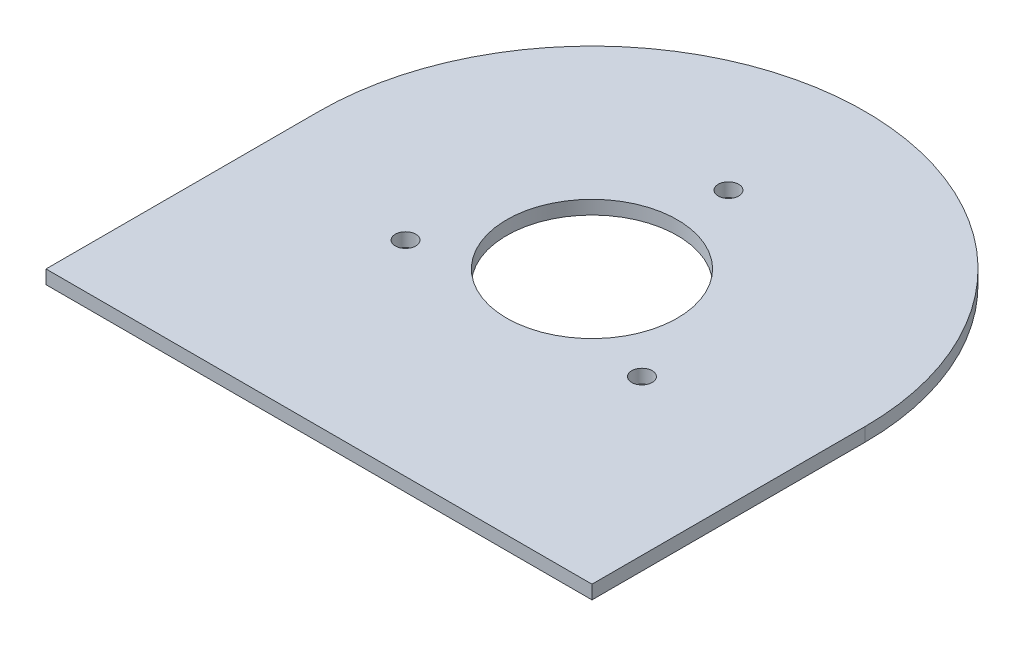
SolidWorks part; units mm, degrees
ref_plane "Front Plane" through (0, 0, 0) normal (0, 0, 1) x (1, 0, 0)
ref_plane "Top Plane" through (0, 0, 0) normal (0, 1, 0) x (1, 0, 0)
ref_plane "Right Plane" through (0, 0, 0) normal (1, 0, 0) x (0, 0, -1)
sketch "Sketch1" plane through (0, 0, 0) normal (0, 1, 0) x (1, 0, 0)
  line L1 (0, 0) -> (80, 0)
  line L2 (0, 0) -> (0, 80)
  line L3 (0, 80) -> (80, 80)
  line L4 (80, 0) -> (80, 80)
  dimension "D1" = 80
  dimension "D2" = 80
extrude "Boss-Extrude1" add sketch "Sketch1" along normal blind 2
sketch "Sketch2" plane through (0, 2, 0) normal (0, 1, 0) x (1, 0, 0)
  circle A0 centre (72, 10.2) radius 2.6 construction
  circle A1 centre (8, 10.2) radius 2.6 construction
  circle A2 centre (72, 10.2) radius 2.6 construction
  circle A3 centre (8, 10.2) radius 2.6 construction
  circle A4 centre (8, 10.2) radius 1.5
  circle A5 centre (72, 10.2) radius 1.5
  dimension "D1" = 3
extrude "Cut-Extrude1" [suppressed] cut sketch "Sketch2" against normal through all
sketch "Sketch3" plane through (0, 2, 0) normal (0, 1, 0) x (1, 0, 0)
  line L0 (0, 80) -> (80, 0) construction
  circle A0 centre (40, 40) radius 12.5
  point P3 (40, 40)
  dimension "D1" = 25
extrude "Cut-Extrude2" cut sketch "Sketch3" against normal through all
sketch "Sketch5" plane through (0, 2, 0) normal (0, 1, 0) x (1, 0, 0)
  line L0 (22.68, 30.0003) -> (0, 30.0003) construction
  line L1 (0, 80) -> (0, 0) construction
  line L2 (57.32, 30.0003) -> (80, 30.0003) construction
  line L3 (80, 0) -> (80, 80) construction
  line L4 (40, 59.9994) -> (22.68, 30.0003) construction
  line L5 (40, 59.9994) -> (57.32, 30.0003) construction
  line L6 (0, 80) -> (80, 0) construction
  line L7 (0, 0) -> (80, 0) construction
  circle A0 centre (22.68, 30.0003) radius 1.5
  circle A1 centre (57.32, 30.0003) radius 1.5
  circle A2 centre (40, 59.9994) radius 1.5
  circle A3 centre (40, 40) radius 19.9994 construction
  point P19 (0, 0)
  point P20 (40, 40)
  dimension "D1" = 3
  dimension "D2" = 34.64
  dimension "D3" = 60
  dimension "D4" = 34.64
extrude "Cut-Extrude3" cut sketch "Sketch5" against normal through all
fillet "Fillet1" 2 edges at (0, 1, -80) (80, 1, -80) type full round first side face at (0, 1, -40) second side face at (80, 1, -40) middle face at (40, 1, -80)
